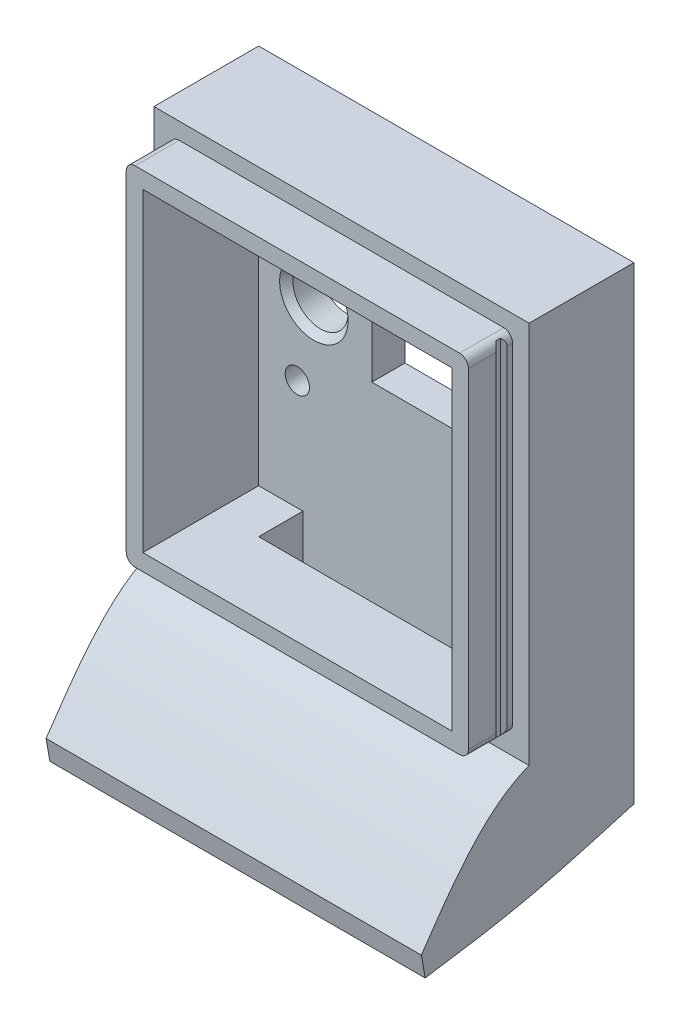
SolidWorks part; units mm, degrees
ref_plane "Front Plane" through (0, 0, 0) normal (0, 0, 1) x (1, 0, 0)
ref_plane "Top Plane" through (0, 0, 0) normal (0, 1, 0) x (1, 0, 0)
ref_plane "Right Plane" through (0, 0, 0) normal (1, 0, 0) x (0, 0, -1)
sketch "Sketch1" plane through (0, 0, 0) normal (0, 0, 1) x (1, 0, 0)
  line L1 (-17, 17.25) -> (17, 17.25)
  line L2 (-17, 17.25) -> (-17, -17.25)
  line L3 (-17, -17.25) -> (17, -17.25)
  line L4 (17, 17.25) -> (17, -17.25)
  line L5 (-17, 17.25) -> (17, -17.25) construction
  line L6 (-17, -17.25) -> (17, 17.25) construction
  point P0 (0, 0)
  dimension "D1" = 34
  dimension "D2" = 34.5
extrude "Boss-Extrude2" add sketch "Sketch1" along normal blind 13.5
shell "Shell1" thickness 3 removed face at (0, 0, 13.5)
sketch "Sketch4" plane through (0, 0, 3) normal (0, 0, 1) x (1, 0, 0)
  line L0 (-10.5, 9.25) -> (-10.5, -4.25) construction
  line L1 (10.5, 9.25) -> (10.5, -4.25) construction
  line L2 (-9, 2.75) -> (9, 2.75) construction
  line L3 (14, 14.25) -> (-14, 14.25) construction
  line L5 (14, -14.25) -> (14, 14.25) construction
  circle A0 centre (-10.5, 9.25) radius 1.1
  circle A1 centre (10.5, 9.25) radius 1.1
  circle A2 centre (10.5, -4.25) radius 1.1
  circle A3 centre (-10.5, -4.25) radius 1.1
  circle A4 centre (-9, 2.75) radius 2.5
  circle A5 centre (9, 2.75) radius 2.5
  dimension "D1" = 13.5
  dimension "D2" = 18
  dimension "D3" = 21
  dimension "D4" = 1.5
  dimension "D5" = 7
  dimension "D6" = 5
  dimension "D7" = 3.5
  dimension "D8" = 5
extrude "Cut-Extrude2" cut sketch "Sketch4" against normal blind 3
chamfer "Chamfer1" distance 0.6 angle 45 2 edges at (11.5, 2.75, 3) (-6.5, 2.75, 3)
sketch "Sketch5" plane through (0, 0, 3) normal (0, 0, 1) x (1, 0, 0)
  line L1 (-3.75, 6.5) -> (3.75, 6.5)
  line L2 (-3.75, 6.5) -> (-3.75, -1)
  line L3 (-3.75, -1) -> (3.75, -1)
  line L4 (3.75, 6.5) -> (3.75, -1)
  line L5 (-3.75, 6.5) -> (3.75, -1) construction
  line L6 (-3.75, -1) -> (3.75, 6.5) construction
  point P0 (0, 2.75)
  dimension "D1" = 7.5
  dimension "D2" = 7.5
extrude "Cut-Extrude4" cut sketch "Sketch5" against normal blind 3
sketch "Sketch6" plane through (0, 0, 13.5) normal (0, 0, 1) x (1, 0, 0)
  line L0 (15.5, 15.75) -> (-15.5, 15.75)
  line L1 (-15.5, 15.75) -> (-15.5, -15.75)
  line L2 (-15.5, -15.75) -> (15.5, -15.75)
  line L3 (15.5, -15.75) -> (15.5, 15.75)
  line L4 (17, 17.25) -> (-17, 17.25)
  line L5 (17, -17.25) -> (17, 17.25)
  line L6 (-17, -17.25) -> (17, -17.25)
  line L7 (-17, 17.25) -> (-17, -17.25)
  line L8 (17, 17.25) -> (-17, 17.25)
  line L9 (17, -17.25) -> (17, 17.25)
  line L10 (-17, -17.25) -> (17, -17.25)
  line L11 (-17, 17.25) -> (-17, -17.25)
  dimension "D1" = 0
  dimension "D2" = 1.5
extrude "Cut-Extrude5" cut sketch "Sketch6" against normal blind 4
fillet "Fillet1" radius 0.8 4 edges at (15.5, -15.75, 11.5) (-15.5, -15.75, 11.5) (-15.5, 15.75, 11.5) (15.5, 15.75, 11.5)
sketch "Sketch7" plane through (0, -15.75, 0) normal (0, -1, 0) x (1, 0, 0)
  line L0 (-13.2774, 13.5) -> (-15.5, 13.5) construction
  line L1 (-14.7, 13.5) -> (14.7, 13.5) construction
  line L2 (-15.5, 13.5) -> (-15.5, 10) construction
  line L3 (-15.5, 9.5) -> (-15.5, 13.5) construction
  line L4 (-15.5, 10) -> (-15.2, 10.3)
  line L5 (-15.2, 10.3) -> (-15.2, 10.7)
  line L6 (-15.2, 10.7) -> (-15.5, 11)
  line L7 (-15.5, 11) -> (-15.5, 10) construction
  line L8 (-15.5, 11) -> (-15.5, 10)
  line L9 (0, 0) -> (0, 14.6019) construction
  line L10 (15.5, 10) -> (15.2, 10.3)
  line L11 (15.2, 10.3) -> (15.2, 10.7)
  line L12 (15.5, 11) -> (15.5, 10)
  line L13 (15.2, 10.7) -> (15.5, 11)
  line L14 (-14.7, 13.5) -> (14.7, 13.5) construction
  point P19 (-14.3887, 13.5)
  dimension "D1" = 1
  dimension "D2" = 0.4
  dimension "D3" = 135
  dimension "D4" = 135
  dimension "D5" = 3.5
extrude "Cut-Extrude6" cut sketch "Sketch7" against normal through all
sketch "Sketch8" plane through (0, -17.25, 0) normal (0, -1, 0) x (1, 0, 0)
  line L0 (-14.7, 9.5) -> (14.7, 9.5) construction
  line L1 (-17, 9.5) -> (17, 9.5)
  line L2 (-17, 9.5) -> (-17, 0)
  line L3 (-17, 0) -> (17, 0)
  line L4 (17, 9.5) -> (17, 0)
  line L5 (-17, 9.5) -> (-17, 0) construction
extrude "Boss-Extrude3" add sketch "Sketch8" along normal blind 8
ref_plane "Plane2" through (0, -2.386, 13.5315) normal (0, -0.1736, 0.9848) x (-1, 0, 0)
sketch "Sketch9" plane through (0, -2.386, 13.5315) normal (0, -0.1736, 0.9848) x (-1, 0, 0)
  line L1 (-17, 25.6864) -> (17, 25.6864)
  line L2 (-17, 25.6864) -> (-17, 15.8941)
  line L3 (-17, 15.8941) -> (17, 15.8941)
  line L4 (17, 25.6864) -> (17, 15.8941)
  line L8 (-17, 23.2167) -> (-17, -18.6376) construction
  line L9 (17, -18.6376) -> (17, 23.2167) construction
ref_plane "Plane3" through (0, -4.1225, 23.3796) normal (0, -0.1736, 0.9848) x (-1, 0, 0)
sketch "Sketch10" plane through (0, -4.1225, 23.3796) normal (0, -0.1736, 0.9848) x (-1, 0, 0)
  line L0 (-17, 24.8664) -> (-17, 23.2167) construction
  line L1 (17, 25.6864) -> (-17, 25.6864)
  line L2 (17, 25.6864) -> (17, 23.6864)
  line L3 (17, 23.6864) -> (-17, 23.6864)
  line L4 (-17, 25.6864) -> (-17, 23.6864)
ref_plane "Plane4" through (0, -0.7614, 4.318) normal (0, -0.1736, 0.9848) x (1, 0, 0)
sketch "Sketch11" plane through (0, -0.7614, 4.318) normal (0, -0.1736, 0.9848) x (1, 0, 0)
  line L4 (-17, -25.6864) -> (17, -25.6864)
  line L5 (-17, -15.8941) -> (-17, -25.6864)
  line L6 (17, -15.8941) -> (-17, -15.8941)
  line L7 (17, -25.6864) -> (17, -15.8941)
  line L8 (-17, -24.8293) -> (17, -24.8293)
  line L9 (-17, -15.8941) -> (-17, -24.8293)
  line L10 (17, -15.8941) -> (-17, -15.8941)
  line L11 (17, -24.8293) -> (17, -15.8941)
  dimension "D1" = 0
loft "Loft1" add profiles "Sketch10", "Sketch9", "Sketch11" connector at (-17, -29.4186, 18.9192) connector at (-17, -27.6821, 9.0712) connector at (-17, -25.2135, 0.0064)
sketch "Sketch2" plane through (0, -14.25, 0) normal (0, 1, 0) x (1, 0, 0)
  line L0 (17, 0) -> (-17, 0) construction
  line L1 (-10, -3) -> (10, -3)
  line L2 (-10, -3) -> (-10, -7)
  line L3 (-10, -7) -> (10, -7)
  line L4 (10, -3) -> (10, -7)
  line L5 (-10, -3) -> (10, -7) construction
  line L6 (-10, -7) -> (10, -3) construction
  point P0 (0, -5)
  dimension "D1" = 20
  dimension "D2" = 4
  dimension "D3" = 3
extrude "Cut-Extrude1" cut sketch "Sketch2" against normal blind 15
